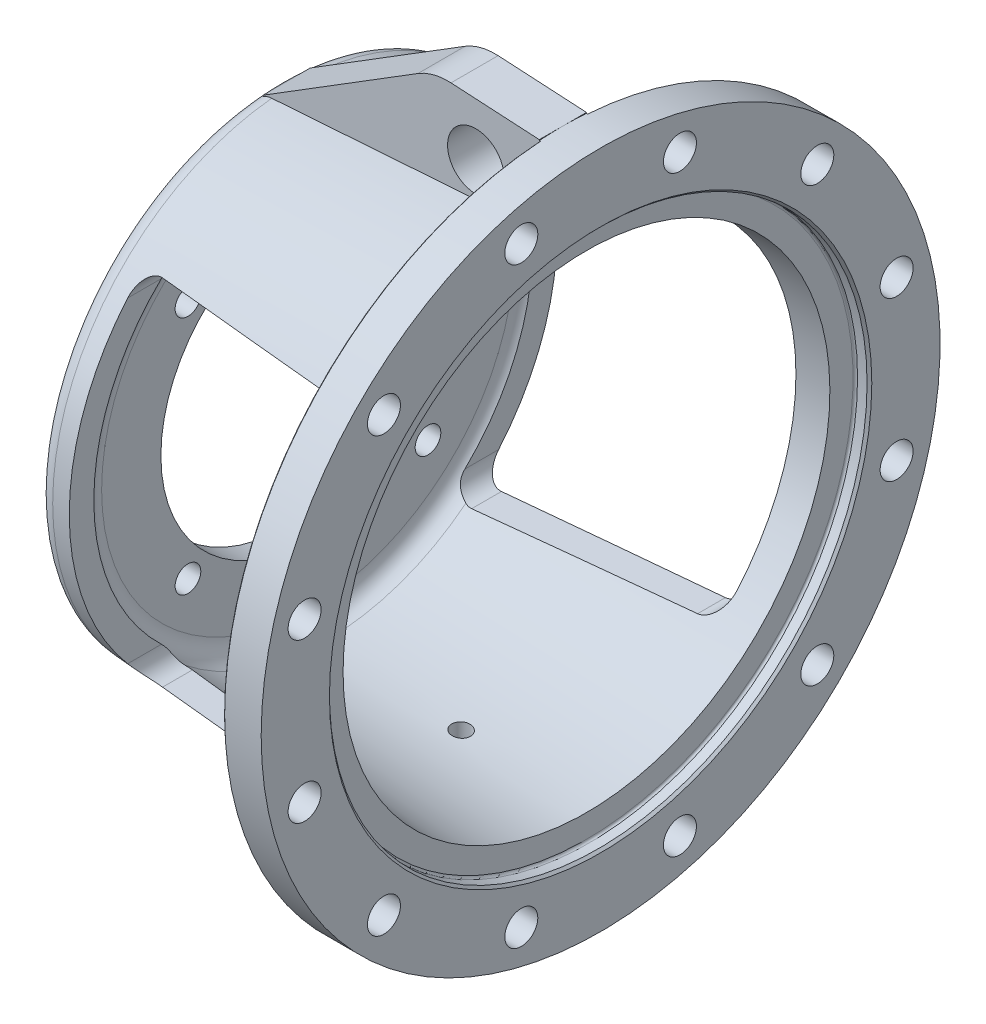
SolidWorks part; units mm, degrees
material "CD4Mc-U Duplex Stainless Steel"
ref_plane "Front Plane" through (0, 0, 0) normal (0, 0, 1) x (1, 0, 0)
ref_plane "Top Plane" through (0, 0, 0) normal (0, 1, 0) x (1, 0, 0)
ref_plane "Right Plane" through (0, 0, 0) normal (1, 0, 0) x (0, 0, -1)
sketch "Sketch2" plane through (0, 0, 0) normal (0, 0, 1) x (1, 0, 0)
  line L0 (0, 0) -> (151.2672, 0) construction
  line L1 (0, 0) -> (0, 150.7291)
  line L2 (11.8141, 163.3982) -> (180.2099, 175.1736)
  line L3 (192.024, 187.8426) -> (192.024, 228.6)
  line L4 (192.024, 228.6) -> (217.424, 228.6)
  line L5 (217.424, 228.6) -> (217.424, 180.975)
  line L6 (207.899, 163.9269) -> (32.1595, 151.638)
  line L7 (20.3454, 138.9689) -> (20.3454, 0)
  line L8 (0, 0) -> (20.3454, 0)
  line L9 (11.8141, 163.3982) -> (206.3963, 163.3982) construction
  line L10 (217.424, 180.975) -> (207.899, 180.975)
  line L11 (207.899, 180.975) -> (207.899, 163.9269)
  arc A0 (0, 150.7291) -> (11.8141, 163.3982) centre (12.7, 150.7291) cw
  arc A1 (180.2099, 175.1736) -> (192.024, 187.8426) centre (179.324, 187.8426) ccw
  arc A2 (32.1595, 151.638) -> (20.3454, 138.9689) centre (33.0454, 138.9689) ccw
  dimension "D1" = 12.7
  dimension "D2" = 163.3982
  dimension "D3" = 151.638
  dimension "D4" = 20.3454
  dimension "D5" = 4
  dimension "D6" = 25.4
  dimension "D7" = 228.6
  dimension "D8" = 217.424
  dimension "D9" = 180.975
  dimension "D10" = 9.525
revolve "Revolve1" add sketch "Sketch2" angle 360 about L0
sketch "Sketch3" plane through (0, 0, 0) normal (-1, 0, 0) x (0, 0, 1)
  circle A0 centre (0, 0) radius 133.4135
  dimension "D1" = 266.827
extrude "Cut-Extrude1" cut sketch "Sketch3" against normal blind 4.7752
sketch "Sketch4" plane through (4.7752, 0, 0) normal (-1, 0, 0) x (0, 0, 1)
  circle A0 centre (0, 0) radius 99.06
  dimension "D1" = 198.12
extrude "Cut-Extrude2" cut sketch "Sketch4" against normal up to next
sketch "Sketch5" plane through (217.424, 0, 0) normal (1, 0, 0) x (0, 0, -1)
  circle A0 centre (0, 0) radius 181.0385
  dimension "D1" = 362.077
extrude "Cut-Extrude3" cut sketch "Sketch5" against normal blind 9.525
sketch "Sketch6" plane through (4.7752, 0, 0) normal (-1, 0, 0) x (0, 0, 1)
  line L0 (0, 0) -> (114.3, 0) construction
  line L1 (0, 0) -> (80.8223, 80.8223) construction
  circle A0 centre (0, 0) radius 114.3 construction
  circle A1 centre (80.8223, 80.8223) radius 8.636
  point P3 (80.8223, 80.8223)
  dimension "D1" = 228.6
  dimension "D3" = 17.272
  dimension "D2" = 45
extrude "Cut-Extrude4" cut sketch "Sketch6" against normal up to next
pattern_circular "CirPattern1" count 4 over 360 about axis through (4.7752, 0, 0) along (-1, 0, 0) of "Cut-Extrude4"
sketch "Sketch7" plane through (217.424, 0, 0) normal (1, 0, 0) x (0, 0, -1)
  line L0 (0, 0) -> (206.375, 0) construction
  line L1 (0, 0) -> (199.3429, 53.4138) construction
  circle A0 centre (0, 0) radius 206.375 construction
  circle A1 centre (199.3429, 53.4138) radius 11.1125
  dimension "D1" = 412.75
  dimension "D3" = 22.225
  dimension "D2" = 15
extrude "Cut-Extrude5" cut sketch "Sketch7" against normal up to next
pattern_circular "CirPattern2" count 12 over 360 about axis through (217.424, 0, 0) along (-1, 0, 0) of "Cut-Extrude5"
sketch "Sketch8" plane through (0, 0, 0) normal (0, 0, 1) x (1, 0, 0)
  line L0 (192.024, 228.6) -> (192.024, -228.6) construction
  line L1 (192.024, 228.6) -> (192.024, 173.461)
  line L2 (5.9873, 161.5101) -> (110.2718, 226.302)
  line L3 (192.024, 228.6) -> (132.5388, 231.9782)
  line L4 (192.024, 173.461) -> (5.4488, 158.5456)
  line L5 (5.4488, 158.5456) -> (5.9873, 161.5101)
  line L6 (192.024, 228.6) -> (192.024, 173.461)
  arc A0 (11.8141, 163.3982) -> (0, 150.7291) centre (12.7, 150.7291) ccw construction
  arc A1 (132.5388, 231.9782) -> (110.2718, 226.302) centre (130.3786, 193.9395) ccw
  dimension "D1" = 76.2
  dimension "D2" = 231.9782
extrude "Boss-Extrude1" add sketch "Sketch8" along normal mid plane 31.75 contours L3 A1 L2 L5 L4 L1 region at (119.8434, 193.7127, 0)
sketch "Sketch9" plane through (0, 0, 15.875) normal (0, 0, 1) x (1, 0, 0)
  line L0 (217.424, -228.6) -> (217.424, 228.6) construction
  circle A0 centre (149.2758, 194.564) radius 19.05
  dimension "D1" = 38.1
  dimension "D2" = 68.1482
  dimension "D3" = 194.564
extrude "Cut-Extrude6" cut sketch "Sketch9" against normal up to next
sketch "Sketch10" plane through (0, 0, 0) normal (0, 1, 0) x (1, 0, 0)
  line L0 (217.424, -228.6) -> (217.424, 228.6) construction
  circle A0 centre (123.444, 0) radius 6.35
  dimension "D2" = 12.7
  dimension "D1" = 93.98
extrude "Cut-Extrude7" cut sketch "Sketch10" against normal up to next
sketch "Sketch11" plane through (0, 0, 0) normal (0, 0, 1) x (1, 0, 0)
  line L0 (0, 150.7291) -> (0, -150.7291) construction
  line L1 (36.5252, -119.3419) -> (173.8376, -119.3419)
  line L2 (23.8252, -106.6419) -> (23.8252, 106.6419)
  line L3 (36.5252, 119.3419) -> (173.8376, 119.3419)
  line L4 (186.5376, -106.6419) -> (186.5376, 106.6419)
  line L5 (23.8252, -119.3419) -> (186.5376, 119.3419) construction
  line L6 (23.8252, 119.3419) -> (186.5376, -119.3419) construction
  arc A0 (36.5252, -119.3419) -> (23.8252, -106.6419) centre (36.5252, -106.6419) cw
  arc A1 (173.8376, -119.3419) -> (186.5376, -106.6419) centre (173.8376, -106.6419) ccw
  arc A2 (173.8376, 119.3419) -> (186.5376, 106.6419) centre (173.8376, 106.6419) cw
  arc A3 (23.8252, 106.6419) -> (36.5252, 119.3419) centre (36.5252, 106.6419) cw
  point P0 (105.1814, 0)
  dimension "D4" = 12.7
  dimension "D1" = 162.7124
  dimension "D2" = 238.6838
  dimension "D3" = 23.8252
extrude "Cut-Extrude8" cut sketch "Sketch11" against normal through all both and the other way through all
chamfer "Chamfer1" distance 1.5875 angle 45 1 edges at (217.424, 0, -181.0385)
chamfer "Chamfer2" distance 0.7937 angle 45 1 edges at (192.024, -228.6, 0)
ref_axis "Axis1" through (149.2758, 194.564, -15.875) along (0, 0, 1)
ref_axis "Axis2" through (123.444, -172.0095, 0) along (0, 1, 0)
sketch "Sketch12" plane through (217.424, 0, 0) normal (1, 0, 0) x (0, 0, -1)
  circle A0 centre (0, 0) radius 180.975
fillet "Fillet1" radius 1.524 1 edges at (207.899, 0, -181.0385)
ref_axis "Axis3" through (149.2758, 194.564, -15.875) along (0, 0, 1)
